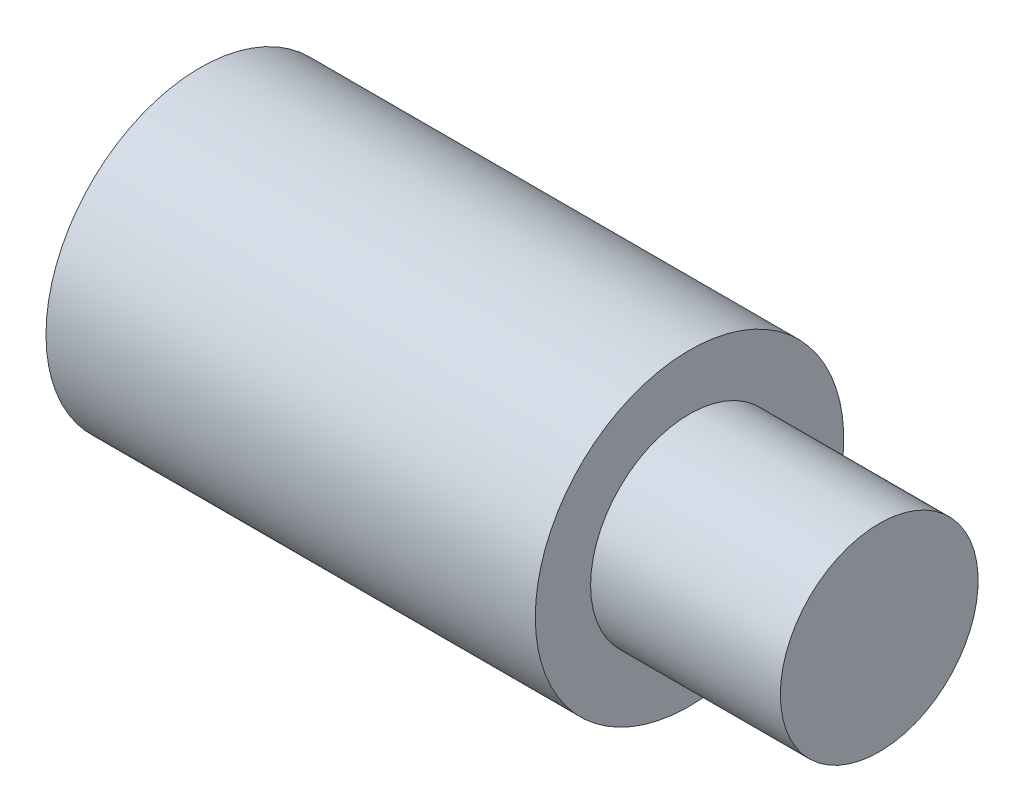
SolidWorks part; units mm, degrees
ref_plane "Front Plane" through (0, 0, 0) normal (0, 0, 1) x (1, 0, 0)
ref_plane "Top Plane" through (0, 0, 0) normal (0, 1, 0) x (1, 0, 0)
ref_plane "Right Plane" through (0, 0, 0) normal (1, 0, 0) x (0, 0, -1)
sketch "Conn_T4_ORB4 Sketch" plane through (0, 0, 0) normal (0, 0, 1) x (1, 0, 0)
  line L0 (-1000, 0) -> (1000, 0) construction
  line L1 (9.5, 0) -> (9.5, 4.953)
  line L2 (9.5, 4.953) -> (0, 4.953)
  line L3 (0, 4.953) -> (0, 7.722)
  line L4 (0, 7.722) -> (-24.5, 7.722)
  line L5 (-24.5, 7.722) -> (-24.5, 0)
  line L6 (-24.5, 0) -> (9.5, 0)
revolve "Conn_T4_ORB4" add sketch "Conn_T4_ORB4 Sketch" angle 360 about L0
ref_axis "Engine Axis" through (11.2, 0, 0) along (-1, 0, 0)
sketch "Socket Sketch" plane through (0, 0, 0) normal (0, 0, 1) x (1, 0, 0)
  line L0 (-1000, 0) -> (1000, 0) construction
  line L1 (-25.5, 0) -> (-25.5, 3.175)
  line L2 (-25.5, 3.175) -> (-9.3, 3.175)
  line L3 (-9.3, 3.175) -> (-9.3, 0)
  line L4 (-9.3, 0) -> (-25.5, 0)
revolve "Socket" cut sketch "Socket Sketch" angle 360 about L0
